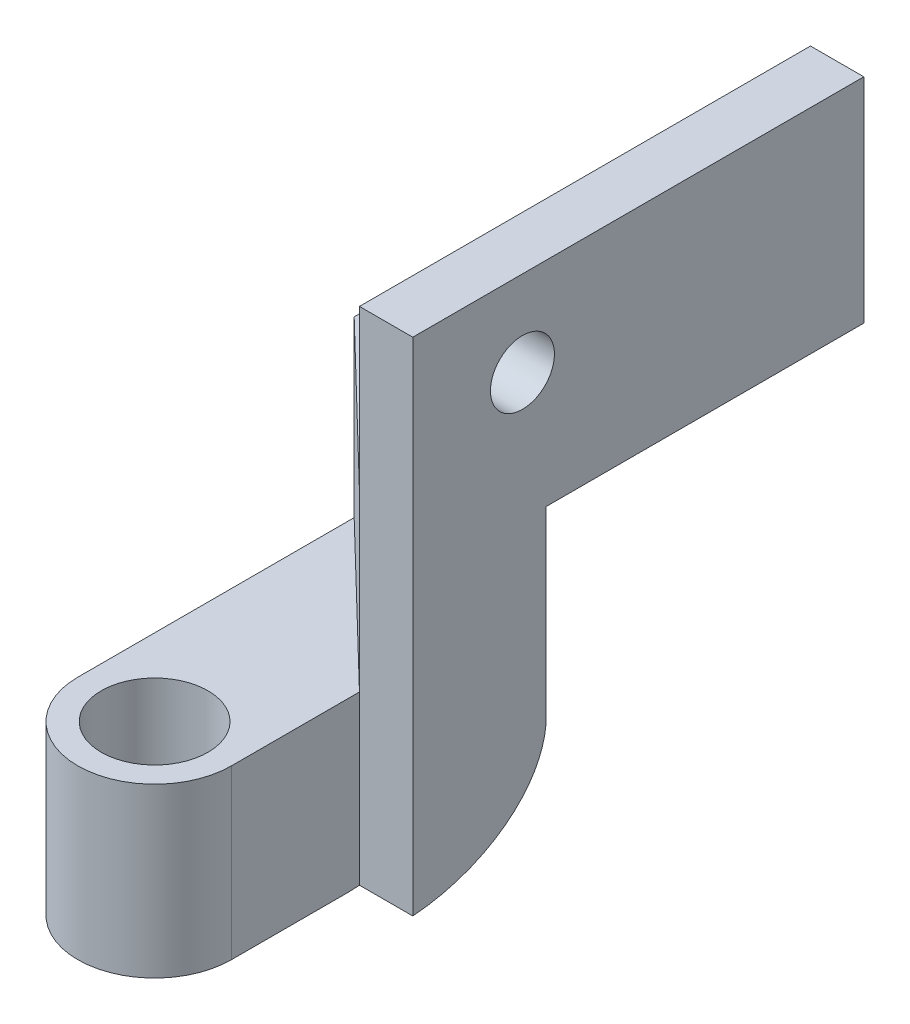
SolidWorks part; units mm, degrees
ref_plane "Front Plane" through (0, 0, 0) normal (0, 0, 1) x (1, 0, 0)
ref_plane "Top Plane" through (0, 0, 0) normal (0, 1, 0) x (1, 0, 0)
ref_plane "Right Plane" through (0, 0, 0) normal (1, 0, 0) x (0, 0, -1)
sketch "Croquis1" plane through (0, 0, 0) normal (0, 1, 0) x (1, 0, 0)
  line L3 (-3.6, 27.14) -> (-3.6, 0)
  line L4 (3.6, 0) -> (3.6, 27.14)
  line L5 (3.6, 27.14) -> (-3.6, 27.14)
  line L6 (-3.6, 12.953) -> (3.6, 6)
  line L7 (0, 0) -> (-2.5, 0) construction
  line L8 (-3.6, 19.2087) -> (3.6, 12.2557)
  arc A3 (-3.6, 0) -> (3.6, 0) centre (0, 0) ccw
  circle A4 centre (0, 0) radius 2.5
  circle A5 centre (-0.4, 21.14) radius 1.5
  dimension "D1" = 3.6
  dimension "D6" = 5
  dimension "D10" = 3
  dimension "D2" = 27.14
  dimension "D7" = 44
  dimension "D8" = 6
  dimension "D9" = 4.5
  dimension "D11" = 6
  dimension "D12" = 4
extrude "Saliente-Extruir1" add sketch "Croquis1" against normal blind 2.5 contours L3 L8 L4 L5 A5 | L8 L3 L6 L4 region at (0, 0, -26.9747) region at (0, 0, -12.6043)
extrude "Saliente-Extruir2" add sketch "Croquis1<4>" against normal blind 7.87 from offset 8.15 separate body contours L3 A3 L4 L6 A4 region at (-0.4356, 0, -4.4478) offset against normal yes
sketch "Croquis1<4>" plane through (0, 0, 0) normal (0, 1, 0) x (1, 0, 0) same geometry as "Croquis1"
extrude "Saliente-Extruir3" add sketch "Croquis1<5>" against normal up to surface (16.02 mm away) contours L8 L3 L6 L4 region at (0, 0, -12.6043) up to face at (0, -16.02, 2.5)
sketch "Croquis1<5>" plane through (0, 0, 0) normal (0, 1, 0) x (1, 0, 0) same geometry as "Croquis1"
fillet "Redondeo1" radius 5 1 edges at (0, -16.02, -15.7322)
sketch "Croquis3" plane through (3.6, 0, 0) normal (1, 0, 0) x (0, 0, -1)
  line L0 (6, -8.15) -> (6, -15.9949)
  line L1 (27.14, 7.5) -> (6, 7.5)
  line L8 (0, -16.02) -> (5.3049, -16.02)
  line L9 (12.2557, -11.02) -> (12.2557, -2.5)
  line L10 (12.2557, -2.5) -> (27.14, -2.5)
  line L11 (27.14, -2.5) -> (27.14, 0)
  line L12 (27.14, 0) -> (6, 0)
  line L13 (6, 0) -> (6, -8.15)
  line L14 (6, -8.15) -> (0, -8.15)
  line L15 (0, -8.15) -> (0, -16.02)
  line L16 (0, -16.02) -> (5.3049, -16.02)
  line L17 (12.2557, -11.02) -> (12.2557, -2.5)
  line L18 (12.2557, -2.5) -> (27.14, -2.5)
  line L19 (27.14, -2.5) -> (27.14, 7.5)
  line L21 (6, 7.5) -> (6, -8.15)
  line L22 (6, -8.15) -> (0, -8.15)
  line L23 (0, -8.15) -> (0, -16.02)
  circle A0 centre (11.14, 3.5) radius 1.5
  ellipse E1 centre (5.3049, -11.02) end of major axis (12.2557, -11.02) minor radius 5 (5.3049, -16.02) -> (12.2557, -11.02) ccw
  ellipse E2 centre (5.3049, -11.02) end of major axis (12.2557, -11.02) minor radius 5 (5.3049, -16.02) -> (12.2557, -11.02) ccw
  ellipse M2 centre (5.3049, -11.02) end of major axis (12.2557, -11.02) minor radius 5 (5.3049, -16.02) -> (12.2557, -11.02) ccw
  line M3 (12.2557, -11.02) -> (12.2557, -2.5)
  line M4 (12.2557, -2.5) -> (27.14, -2.5)
  line M5 (27.14, -2.5) -> (27.14, 0)
  line M6 (27.14, 0) -> (6, 0)
  line M7 (6, 0) -> (6, -8.15)
  dimension "D5" = 3
  dimension "D2" = 10
  dimension "D3" = 16
  dimension "D4" = 4
  dimension "D1" = 0
extrude "Saliente-Extruir4" add sketch "Croquis3" along normal blind 2.5 contours L0 M7 M2 M3 M4 M5 M6 | L1 L21 L19 A0 M6 region at (3.6, -5.6795, -12.0634) region at (3.6, 3.7617, -16.8234)
equation "\"D1@Saliente-Extruir2\"=7.87"
